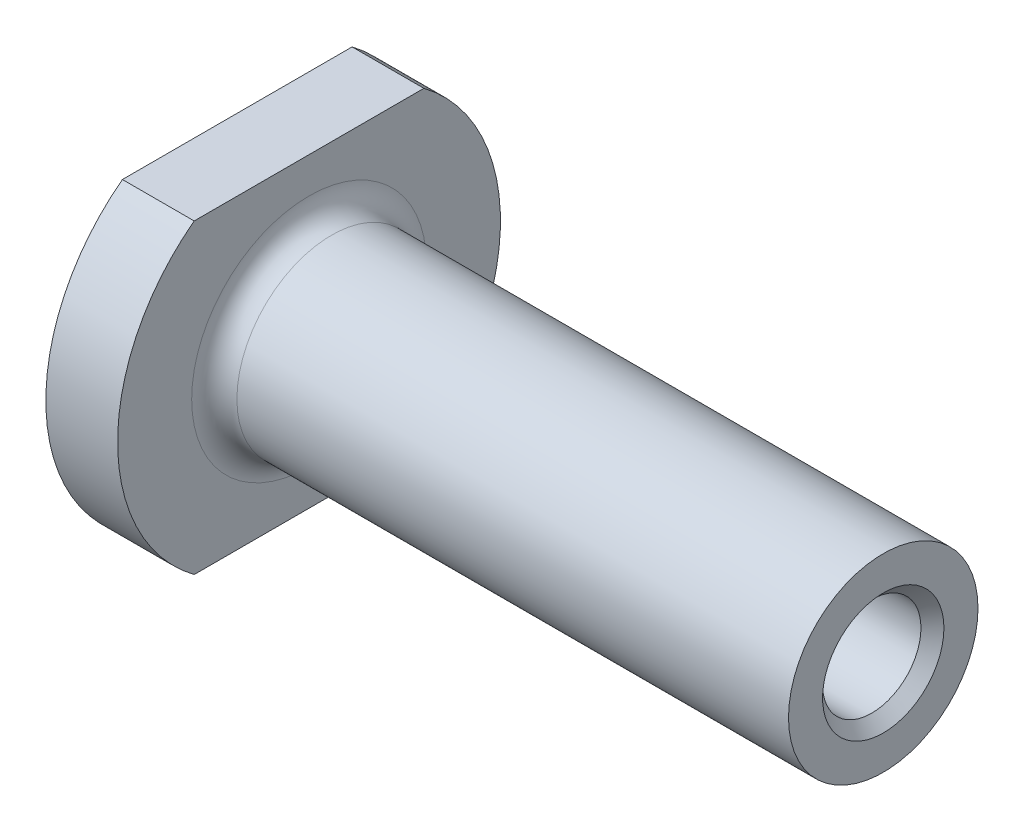
SolidWorks part; units mm, degrees
material "Alloy Steel"
ref_plane "Front Plane" through (0, 0, 0) normal (0, 0, 1) x (1, 0, 0)
ref_plane "Top Plane" through (0, 0, 0) normal (0, 1, 0) x (1, 0, 0)
ref_plane "Right Plane" through (0, 0, 0) normal (1, 0, 0) x (0, 0, -1)
sketch "Sketch1" plane through (0, 0, 0) normal (0, 0, 1) x (1, 0, 0)
  line L0 (0, 0) -> (-17.6508, 0) construction
  line L1 (0, 0) -> (42.8625, 0)
  line L2 (42.8625, 0) -> (42.8625, 6.2865)
  line L3 (42.8625, 6.2865) -> (4.7625, 6.2865)
  line L4 (4.7625, 6.2865) -> (4.7625, 12.7)
  line L5 (4.7625, 12.7) -> (0, 12.7)
  line L6 (0, 12.7) -> (0, 0)
  dimension "D1" = 12.573
  dimension "D2" = 42.8625
  dimension "D3" = 4.7625
  dimension "D4" = 25.4
revolve "Revolve1" add sketch "Sketch1" angle 360 about L0
fillet "Fillet1" radius 1.5 1 edges at (4.7625, 0, -6.2865)
hole_wizard "5/16-18" positions "Sketch2" profile "Sketch3" tap size "5/16-18" standard "ANSI Inch" end condition through all
sketch "Sketch2" plane through (42.8625, 0, 0) normal (1, 0, 0) x (0, 0, -1)
  point P0 (0, 0)
sketch "Sketch3" plane through (42.8625, 0, 0) normal (0, 1, 0) x (0, 0, -1)
  line L0 (0, 0) -> (0, 42.8625)
  line L1 (0, 42.8625) -> (3.2639, 42.8625)
  line L2 (3.2639, 42.8625) -> (3.2639, 0)
  line L5 (3.2639, 0) -> (0, 0)
  line L11 (0, -6.35) -> (0, 107.95) construction
  dimension "Thru Tap Drill Dia." = 6.5278
  dimension "Thru Tap Drill Depth" = 42.8625
cosmetic thread "Hole Thread1" parameters "D2"=7.9375
sketch "Sketch4" plane through (0, 0, 0) normal (-1, 0, 0) x (0, 0, 1)
  line L0 (-7.62, 10.16) -> (7.62, 10.16)
  line L5 (7.62, -10.16) -> (-7.62, -10.16)
  arc A1 (7.62, 10.16) -> (-7.62, 10.16) centre (0, 0) ccw
  circle A2 centre (0, 0) radius 12.7
  arc A3 (-7.62, -10.16) -> (7.62, -10.16) centre (0, 0) ccw
  point P4 (0, 12.7)
  dimension "D1" = 0
  dimension "D2" = 2.54
extrude "Cut-Extrude1" cut sketch "Sketch4" against normal through all
chamfer "Chamfer1" distance 0.762 angle 45 2 edges at (0, 0, -3.2639) (42.8625, 0, -3.2639)
equation "\"D1@Sketch1\"=0.500000-.005"
